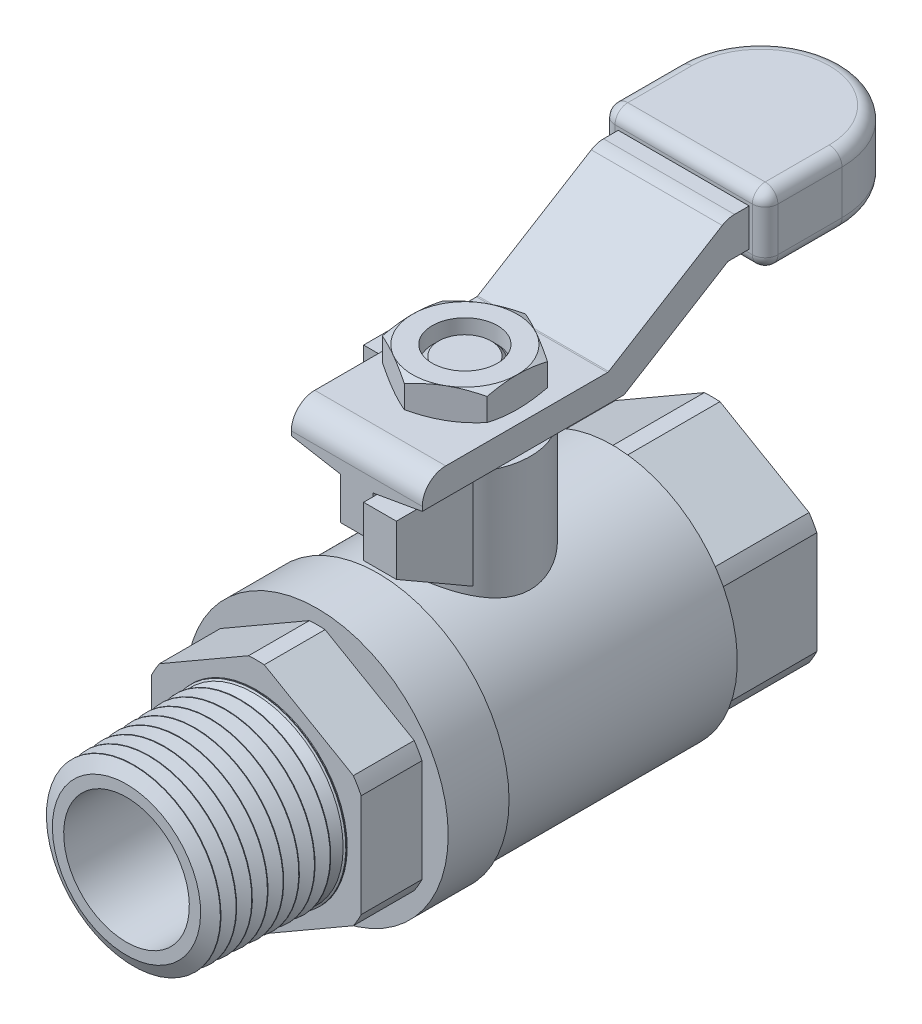
SolidWorks part; units mm, degrees
ref_plane "Front" through (0, 0, 0) normal (0, 0, 1) x (1, 0, 0)
ref_plane "Top" through (0, 0, 0) normal (0, 1, 0) x (1, 0, 0)
ref_plane "Right" through (0, 0, 0) normal (1, 0, 0) x (0, 0, -1)
sketch "Sketch1" plane through (0, -2.9295, 125.5668) normal (1, 0, 0) x (0, 0, -1)
  line L0 (139.5622, 2.9295) -> (139.5622, 11.7701)
  line L1 (139.5622, 11.7701) -> (140.4199, 13.3689) construction
  line L2 (140.4199, 13.3689) -> (141.3756, 11.8268) construction
  line L3 (141.3756, 11.8268) -> (142.2333, 13.4256) construction
  line L4 (142.2333, 13.4256) -> (143.189, 11.8835) construction
  line L5 (141.4083, 11.8877) -> (142.2006, 13.3646)
  line L6 (142.2006, 13.3646) -> (142.2697, 13.3668)
  line L7 (142.2697, 13.3668) -> (143.1526, 11.9422)
  line L8 (143.1526, 11.9422) -> (143.2217, 11.9444)
  line L9 (139.5622, 11.7701) -> (143.189, 11.8835) construction
  line L10 (140.4199, 13.3689) -> (142.2333, 13.4256) construction
  line L11 (139.9911, 12.5695) -> (142.7112, 12.6545) construction
  line L12 (139.5622, 2.9295) -> (125.5668, 2.9295) construction
  line L13 (143.2217, 11.9444) -> (144.014, 13.4213)
  line L14 (139.5949, 11.8311) -> (140.3872, 13.3079)
  line L15 (140.3872, 13.3079) -> (140.4563, 13.3101)
  line L16 (140.4563, 13.3101) -> (141.3392, 11.8856)
  line L17 (141.3392, 11.8856) -> (141.4083, 11.8877)
  line L18 (139.9911, 12.5695) -> (139.5622, 12.5561) construction
  line L19 (139.5622, 12.5561) -> (139.5622, 11.7701) construction
  line L20 (139.9911, -6.7105) -> (139.5622, -6.6971) construction
  line L21 (139.5949, 11.8311) -> (139.5622, 11.7701)
  line L22 (144.014, 13.4213) -> (144.0831, 13.4234)
  line L23 (144.0831, 13.4234) -> (144.966, 11.9989)
  line L24 (144.966, 11.9989) -> (145.0351, 12.0011)
  line L25 (145.0351, 12.0011) -> (145.8274, 13.478)
  line L26 (145.8274, 13.478) -> (145.8965, 13.4801)
  line L27 (145.8965, 13.4801) -> (146.7794, 12.0556)
  line L28 (146.7794, 12.0556) -> (146.8485, 12.0577)
  line L29 (146.8485, 12.0577) -> (147.6408, 13.5346)
  line L30 (147.6408, 13.5346) -> (147.7099, 13.5368)
  line L31 (147.7099, 13.5368) -> (148.5928, 12.1123)
  line L32 (148.5928, 12.1123) -> (148.6619, 12.1144)
  line L33 (148.6619, 12.1144) -> (149.4542, 13.5913)
  line L34 (149.4542, 13.5913) -> (149.5233, 13.5935)
  line L35 (149.5233, 13.5935) -> (150.4062, 12.1689)
  line L36 (150.4062, 12.1689) -> (150.4753, 12.1711)
  line L37 (150.4753, 12.1711) -> (151.2676, 13.648)
  line L38 (151.2676, 13.648) -> (151.3367, 13.6501)
  line L39 (151.3367, 13.6501) -> (152.2196, 12.2256)
  line L40 (152.2196, 12.2256) -> (152.2887, 12.2278)
  line L41 (152.2887, 12.2278) -> (153.081, 13.7046)
  line L42 (153.081, 13.7046) -> (153.1501, 13.7068)
  line L43 (153.1501, 13.7068) -> (154.033, 12.2823)
  line L44 (154.033, 12.2823) -> (154.1021, 12.2844)
  line L45 (154.1021, 12.2844) -> (154.8944, 13.7613)
  line L46 (154.8944, 13.7613) -> (154.9635, 13.7635)
  line L47 (154.9635, 13.7635) -> (155.8464, 12.3389)
  line L48 (155.8464, 12.3389) -> (155.9155, 12.3411)
  line L49 (155.9155, 12.3411) -> (156.7078, 13.818)
  line L50 (156.7078, 13.818) -> (156.7769, 13.8201)
  line L51 (156.7769, 13.8201) -> (157.6598, 12.3956)
  line L52 (157.6598, 12.3956) -> (157.7289, 12.3978)
  line L53 (157.7289, 12.3978) -> (158.5212, 13.8747)
  line L54 (158.5212, 13.8747) -> (158.5903, 13.8768)
  line L55 (158.5903, 13.8768) -> (159.4732, 12.4523)
  line L56 (159.4732, 12.4523) -> (159.5423, 12.4544)
  line L57 (159.5423, 12.4544) -> (160.3346, 13.9313)
  line L58 (160.3346, 13.9313) -> (160.4037, 13.9335)
  line L59 (160.4037, 13.9335) -> (161.2866, 12.509)
  line L60 (161.2866, 12.509) -> (161.3557, 12.5111)
  line L61 (161.3557, 12.5111) -> (162.148, 13.988)
  line L62 (162.148, 13.988) -> (162.2171, 13.9902)
  line L63 (162.2171, 13.9902) -> (163.1, 12.5656)
  line L64 (163.1, 12.5656) -> (163.1691, 12.5678)
  line L65 (163.1691, 12.5678) -> (163.9614, 14.0447)
  line L66 (163.9614, 14.0447) -> (164.0305, 14.0468)
  line L67 (164.0305, 14.0468) -> (164.9134, 12.6223)
  line L68 (164.9134, 12.6223) -> (164.9825, 12.6245)
  line L69 (164.9825, 12.6245) -> (165.7748, 14.1013)
  line L70 (165.7748, 14.1013) -> (165.8439, 14.1035)
  line L71 (165.8439, 14.1035) -> (166.7268, 12.679)
  line L72 (166.7268, 12.679) -> (166.7959, 12.6811)
  line L73 (139.5622, 2.9295) -> (166.7959, 2.9295)
  line L74 (166.7959, 2.9295) -> (166.7959, 12.6811)
  line L75 (140.4217, 13.309) -> (140.4199, 13.3689) construction
  line L76 (142.7112, 12.6545) -> (153.1258, 12.98) construction
  line L77 (153.1258, 12.98) -> (153.1258, 2.9295) construction
  line L78 (153.1258, 12.98) -> (155.0562, 13.0403) construction
  line L79 (155.0562, 13.0403) -> (155.0562, 2.9295) construction
  line L80 (125.5668, 2.9295) -> (85.2062, 2.9295) construction
  line L82 (85.2062, 2.9295) -> (85.2062, 13.0403) construction
  line L84 (153.1258, 12.2539) -> (155.0562, 12.3143) construction
  line L85 (139.5622, 7.3498) -> (125.5668, 7.3498) construction
  line L86 (125.5668, 7.3498) -> (125.5668, 2.9295) construction
  line L87 (155.0562, 13.0403) -> (85.2062, 13.0403) construction
  dimension "D1" = 60
  dimension "E0" = 19.2532
  dimension "Thread Pitch" = 1.8143
  dimension "D4" = 3.58
  dimension "L2 Thread Engagement" = 13.5636
  dimension "l Thread Length" = 15.494
  dimension "Body Length" = 69.85
  dimension "Right Length G" = 29.4894
  dimension "D5" = 54.356
revolve "Revolve1" add sketch "Sketch1" angle 360 about L12
sketch "Sketch6" plane through (0, 0, 0) normal (1, 0, 0) x (0, 0, -1)
  line L0 (29.4894, 0) -> (29.4894, 10.8369)
  line L1 (29.4894, 10.8369) -> (41.2291, 11.2038)
  line L2 (41.2291, 11.2038) -> (41.2291, 0)
  line L3 (41.2291, 0) -> (29.4894, 0)
  line L4 (29.4894, 10.1108) -> (29.4894, 0) construction
  line L5 (13.9954, 0) -> (41.2291, 0) construction
  line L6 (41.2291, 0) -> (41.2291, 9.7516) construction
  line L7 (31.1409, 10.8885) -> (31.2101, 10.8906) construction
revolve "Cut-Revolve3" cut sketch "Sketch6" angle 360 about L3
sketch "Sketch7" plane through (0, 0, 0) normal (1, 0, 0) x (0, 0, -1)
  line L0 (27.559, 9.3244) -> (29.4894, 10.8369)
  line L1 (29.4894, 10.8369) -> (29.4894, 9.3847)
  line L2 (29.4894, 9.3847) -> (27.559, 9.3244)
  line L3 (29.4894, 10.1108) -> (29.4894, 0) construction
  line L4 (14.8203, 10.3784) -> (14.8895, 10.3806) construction
  line L5 (27.559, 9.3244) -> (29.4894, 9.3847) construction
  line L6 (13.9954, 0) -> (27.559, 0) construction
  line L7 (27.559, 0) -> (27.559, 9.3244) construction
  line L8 (13.9954, 0) -> (13.9954, 8.8406) construction
  line L9 (0, 0) -> (13.9954, 0) construction
  line L10 (0, 0) -> (0, 7.493) construction
  line L11 (0, 7.493) -> (12.6478, 7.493) construction
  line L12 (13.9954, 0) -> (13.9954, 8.8406) construction
  line L13 (13.9954, 8.8406) -> (12.6478, 7.493) construction
  dimension "D1" = 45
  dimension "Min ID" = 14.986
revolve "Revolve3" add sketch "Sketch7" angle 360 about L6
pattern_linear "LPattern2" count 2 spacing 54.356 along (0, 0, 1) of bodies 114
sketch "Sketch30" plane through (0, 0, 0) normal (1, 0, 0) x (0, 0, -1)
  line L0 (-40.3606, 0) -> (-40.3606, 10.1108) construction
  line L1 (-40.3606, 7.493) -> (0, 7.493)
  line L2 (-40.3606, 7.493) -> (-40.3606, 0)
  line L3 (-40.3606, 0) -> (0, 0)
  line L4 (0, 7.493) -> (0, 0)
  line L5 (0, 7.493) -> (12.6478, 7.493) construction
  line L6 (13.9954, 0) -> (0, 0) construction
  line L7 (0, 4.4203) -> (0, 0) construction
revolve "Cut-Revolve8" cut sketch "Sketch30" angle 360 about L3
sketch "Sketch29" plane through (0, 0, 0) normal (1, 0, 0) x (0, 0, -1)
  line L0 (0, 0) -> (13.9954, 0) construction
  line L1 (13.9954, 0) -> (13.9954, 8.8406) construction
  line L2 (0, 7.493) -> (12.6478, 7.493) construction
  line L3 (13.9954, 8.8406) -> (12.6478, 7.493) construction
  line L4 (-24.8666, 0) -> (13.9954, 0)
  line L5 (13.9954, 0) -> (13.9954, 8.8406)
  line L6 (-24.8666, 7.493) -> (12.6478, 7.493)
  line L7 (13.9954, 8.8406) -> (12.6478, 7.493)
  line L8 (-24.8666, -10.8369) -> (-24.8666, 10.8369) construction
  line L9 (-24.8666, 0) -> (-24.8666, 7.493)
revolve "Revolve6" add sketch "Sketch29" angle 360 about L4
sketch "Sketch8" plane through (0, 0, 24.8666) normal (0, 0, 1) x (1, 0, 0)
  line L1 (0, 14.4301) -> (-12.4968, 7.215)
  line L2 (-12.4968, 7.215) -> (-12.4968, -7.215)
  line L3 (-12.4968, -7.215) -> (0, -14.4301)
  line L4 (0, -14.4301) -> (12.4968, -7.215)
  line L5 (12.4968, -7.215) -> (12.4968, 7.215)
  line L6 (12.4968, 7.215) -> (0, 14.4301)
  circle A0 centre (0, 0) radius 12.4968 construction
  dimension "Body Hex" = 24.9936
extrude "Extrude1" add sketch "Sketch8" against normal up to surface (54.356 mm away) separate body
sketch "Sketch9" plane through (0, 0, 0) normal (1, 0, 0) x (0, 0, -1)
  line L0 (-17.6095, 7.215) -> (-17.6095, 15.621)
  line L1 (-17.6095, 15.621) -> (-10.3523, 15.621)
  line L2 (-10.3523, 15.621) -> (-10.3523, 15.1811)
  line L3 (-10.3523, 15.1811) -> (-10.0412, 14.87)
  line L4 (-10.0412, 14.87) -> (17.624, 14.87)
  line L5 (17.624, 14.87) -> (17.624, 7.215)
  line L6 (17.624, 7.215) -> (-17.6095, 7.215)
  line L7 (29.4894, 7.215) -> (-24.8666, 7.215) construction
  line L8 (0, 0) -> (0, 7.215) construction
  line L9 (13.9954, 0) -> (13.9954, 8.8406) construction
  line L10 (0, 0) -> (-17.6095, 0) construction
  line L11 (-17.6095, 0) -> (-17.6095, 7.215) construction
  line L12 (-10.0412, 14.87) -> (-10.0412, 14.4301) construction
  line L13 (29.4894, 14.4301) -> (-24.8666, 14.4301) construction
  line L14 (29.4894, 10.1108) -> (29.4894, 14.87) construction
  line L15 (29.4894, 14.87) -> (17.624, 14.87) construction
  line L16 (-24.8666, 14.4301) -> (-24.8666, 15.621) construction
  line L17 (-24.8666, 15.621) -> (-17.6095, 15.621) construction
  dimension "D1" = 3.6286
  dimension "D2" = 31.242
  dimension "D3" = 135
  dimension "D4" = 7.2571
revolve "Revolve4" add sketch "Sketch9" angle 360 about L10
sketch "Sketch10" plane through (0, 0, 0) normal (1, 0, 0) x (0, 0, -1)
  line L0 (0, 7.493) -> (0, 23.8567)
  line L1 (3.8925, 26.4221) -> (3.9179, 26.4221) construction
  line L2 (7.8105, 26.4221) -> (7.8105, 7.493)
  line L3 (7.8105, 7.493) -> (0, 7.493)
  line L4 (0, 0) -> (0, 7.493) construction
  line L5 (-9.0805, 21.1485) -> (-9.0805, 26.6761) construction
  line L6 (-9.0805, 26.6761) -> (10.3505, 26.6761) construction
  line L7 (10.3505, 26.6761) -> (23.5567, 34.7738) construction
  line L8 (-9.0805, 21.1485) -> (-12.8905, 21.1485) construction
  line L9 (-12.8905, 21.1485) -> (-12.8905, 30.4861) construction
  line L10 (-12.8905, 30.4861) -> (9.2754, 30.4861) construction
  line L11 (9.2754, 30.4861) -> (23.5567, 39.243) construction
  line L12 (23.5567, 39.243) -> (23.5567, 34.7738) construction
  line L13 (17.624, 14.87) -> (-10.0412, 14.87) construction
  line L14 (23.5567, 41.148) -> (23.5567, 32.8688) construction
  line L15 (23.5567, 32.8688) -> (44.9834, 32.8688) construction
  line L16 (44.9834, 32.8688) -> (44.9834, 41.148) construction
  line L17 (44.9834, 41.148) -> (23.5567, 41.148) construction
  line L18 (-1.8075, 30.4861) -> (-1.8075, 26.6761) construction
  line L19 (16.416, 34.8645) -> (18.4076, 31.6165) construction
  line L20 (-7.8105, 26.4221) -> (-7.8105, 7.493) construction
  line L21 (0, 7.493) -> (12.6478, 7.493) construction
  line L22 (23.5567, 32.8688) -> (23.5567, 14.87) construction
  line L23 (29.4894, 14.87) -> (17.624, 14.87) construction
  line L24 (-10.3523, 15.621) -> (-10.3523, 21.1485) construction
  line L25 (-10.3523, 21.1485) -> (-12.8905, 21.1485) construction
  line L26 (3.8925, 26.4221) -> (3.8925, 32.8688)
  line L27 (3.8925, 32.8688) -> (0, 32.8688)
  line L28 (3.8925, 26.4221) -> (3.8925, 23.8821)
  line L29 (3.8925, 23.8821) -> (0, 23.8821)
  line L30 (0, 23.8567) -> (3.9179, 23.8567)
  line L31 (3.9179, 23.8567) -> (3.9179, 26.4221)
  line L32 (3.9179, 26.4221) -> (7.8105, 26.4221)
  line L33 (0, 23.8567) -> (0, 23.8821) construction
  line L34 (0, 23.8821) -> (0, 32.8688)
  line L35 (-3.8925, 26.4221) -> (-3.8925, 32.8688) construction
  line L36 (3.9179, 23.8567) -> (3.9179, 14.87) construction
  line L37 (3.9179, 14.87) -> (23.5567, 14.87) construction
  point P26 (23.5567, 37.0084)
  dimension "Handle Height" = 41.148
  dimension "Handle Length" = 44.9834
  dimension "D3" = 15.621
  dimension "D5" = 17.9988
  dimension "D6" = 3.81
  dimension "D7" = 1.27
  dimension "D8" = 0.254
  dimension "D9" = 2.54
  dimension "D11" = 0.0254
  dimension "D12" = 0.0254
  dimension "D13" = 8.9867
  dimension "D14" = 2.54
  dimension "D2" = 1.905
revolve "Revolve5" add sketch "Sketch10" angle 360 about L4
chamfer "Chamfer1" distance 0.762 angle 45 1 edges at (0, 32.8688, -3.8925)
sketch "Sketch20" plane through (0, 0, 0) normal (1, 0, 0) x (0, 0, -1)
  line L0 (3.8925, 32.8688) -> (-3.8926, 32.8688) construction
  line L1 (-3.8926, 32.8688) -> (-3.8925, 32.075) construction
  line L2 (-3.8925, 32.075) -> (3.8925, 32.8688) construction
  line L3 (3.8925, 32.8688) -> (3.9026, 32.7701) construction
  line L4 (3.9026, 32.7701) -> (3.9731, 32.0791)
  line L5 (3.9731, 32.0791) -> (3.5205, 32.2823)
  line L6 (3.5205, 32.2823) -> (3.5004, 32.4797)
  line L7 (3.5004, 32.4797) -> (3.9026, 32.7701)
  line L8 (3.5104, 32.381) -> (3.9378, 32.4246) construction
  line L9 (3.8925, 32.8688) -> (3.8926, 32.42) construction
  line L10 (3.8926, 32.42) -> (-3.8925, 31.6262) construction
  line L11 (-3.8925, 31.6262) -> (-3.8925, 32.075) construction
  line L12 (-0.0862, 32.8688) -> (0.0862, 31.1774) construction
  line L13 (-3.8925, 26.4221) -> (-3.8925, 32.8688) construction
  line L14 (3.8925, 26.4221) -> (3.8925, 32.8688) construction
  line L15 (3.8925, 32.8688) -> (0, 32.8688) construction
  point P13 (0, 32.0231)
  dimension "D2" = 0.1984
  dimension "D3" = 0.7937
  dimension "D4" = 60
  dimension "D5" = 0.7937
revolve "Cut-Revolve6" cut sketch "Sketch20" angle 360 about L12
pattern_linear "LPattern1" count 2 spacing 0.7937 along (0, 1, 0) count 11 spacing 0.7937 along (0, -1, 0) of "Cut-Revolve6"
sketch "Sketch26" plane through (0, 23.8567, 0) normal (0, 1, 0) x (-1, 0, 0)
  circle A1 centre (0, 0) radius 3.9179
  circle A2 centre (0, 0) radius 3.9179
  dimension "D1" = 0
extrude "Extrude8" add sketch "Sketch26" along normal blind 0.127
sketch "Sketch16" plane through (0, 0, 0) normal (1, 0, 0) x (0, 0, -1)
  line L0 (-24.8666, 7.215) -> (-24.8666, 14.4301) construction
  line L1 (29.4894, 14.4301) -> (17.624, 14.4301)
  line L2 (29.4894, 14.4301) -> (29.4894, 13.9221)
  line L3 (29.4894, 13.9221) -> (17.624, 13.9221)
  line L4 (17.624, 14.4301) -> (17.624, 13.9221)
  line L5 (-24.8666, 14.4301) -> (-17.6095, 14.4301)
  line L6 (-24.8666, 14.4301) -> (-24.8666, 13.9221)
  line L7 (-24.8666, 13.9221) -> (-17.6095, 13.9221)
  line L8 (-17.6095, 14.4301) -> (-17.6095, 13.9221)
  line L9 (29.4894, 14.4301) -> (29.4894, 7.215) construction
  line L10 (17.624, -14.87) -> (17.624, 14.87) construction
  line L11 (-17.6095, 15.621) -> (-17.6095, -15.621) construction
  line L12 (-17.6095, 14.4301) -> (-24.8666, 14.4301) construction
  line L13 (0, 0) -> (-24.8666, 0) construction
  line L14 (-24.8666, 0) -> (-24.8666, 13.9221) construction
  dimension "D1" = 0.508
revolve "Cut-Revolve5" cut sketch "Sketch16" angle 360 about L13
combine bodies "Combine1" operation type subtract main body 126 bodies to subtract 151
combine bodies "Combine2" operation type add bodies to combine 150 123
sketch "Sketch11" plane through (0, 0, 0) normal (1, 0, 0) x (0, 0, -1)
  line L1 (9.2754, 30.4861) -> (23.5567, 39.243) construction
  line L2 (10.3505, 26.6761) -> (23.5567, 34.7738) construction
  line L3 (-9.0805, 26.6761) -> (10.3505, 26.6761) construction
  line L4 (-9.0805, 21.1485) -> (-9.0805, 26.6761) construction
  line L5 (-12.8905, 30.4861) -> (9.2754, 30.4861) construction
  line L6 (-12.8905, 21.1485) -> (-12.8905, 30.4861) construction
  line L7 (43.0784, 34.7738) -> (43.0784, 39.243)
  line L8 (9.2754, 30.4861) -> (23.5567, 39.243)
  line L9 (10.3505, 26.6761) -> (23.5567, 34.7738)
  line L10 (-9.0805, 26.6761) -> (10.3505, 26.6761)
  line L11 (-9.0805, 21.1485) -> (-9.0805, 26.6761)
  line L12 (-12.8905, 30.4861) -> (9.2754, 30.4861)
  line L13 (-12.8905, 21.1485) -> (-12.8905, 30.4861)
  line L14 (-9.0805, 21.1485) -> (-12.8905, 21.1485) construction
  line L15 (-9.0805, 21.1485) -> (-12.8905, 21.1485)
  line L16 (23.5567, 39.243) -> (43.0784, 39.243)
  line L17 (23.5567, 34.7738) -> (43.0784, 34.7738)
  line L18 (44.9834, 32.8688) -> (44.9834, 41.148) construction
  dimension "D1" = 1.905
extrude "Extrude2" add sketch "Sketch11" along normal mid plane 15.621 separate body
sketch "Sketch21" plane through (0, 30.4861, 0) normal (0, 1, 0) x (-1, 0, 0)
  circle A0 centre (0, 0) radius 3.918
extrude "Cut-Extrude1" cut sketch "Sketch21" against normal through all
fillet "Fillet1" radius 0.254 3 edges at (0, 34.7738, -23.5567) (0, 30.4861, -9.2754) (0, 26.6761, 9.0805)
fillet "Fillet2" radius 2.794 3 edges at (0, 30.4861, 12.8905) (0, 39.243, -23.5567) (0, 26.6761, -10.3505)
fillet "Fillet3" radius 7.8105 2 edges at (-7.8105, 37.0084, -43.0784) (7.8105, 37.0084, -43.0784)
sketch "Sketch12" plane through (0, 39.243, 0) normal (0, 1, 0) x (-1, 0, 0)
  line L0 (9.7155, -26.0967) -> (-9.7155, -26.0967)
  line L1 (-9.7155, -26.0967) -> (-9.7155, -35.2679)
  line L2 (9.7155, -35.2679) -> (9.7155, -26.0967)
  line L3 (-7.8105, -35.2679) -> (-7.8105, -24.3451) construction
  line L4 (0, -44.9834) -> (0, -23.5567) construction
  arc A0 (-9.7155, -35.2679) -> (9.7155, -35.2679) centre (0, -35.2679) ccw
  arc A1 (-7.8105, -35.2679) -> (0, -43.0784) centre (0, -35.2679) ccw construction
  dimension "D1" = 1.905
  dimension "D2" = 2.54
extrude "Extrude3" add sketch "Sketch12" along normal blind 1.905 separate body
sketch "Sketch13" plane through (0, 34.7738, 0) normal (0, -1, 0) x (1, 0, 0)
  line L3 (9.7155, -26.0967) -> (-9.7155, -26.0967)
  line L4 (9.7155, -35.2679) -> (9.7155, -26.0967)
  line L5 (-9.7155, -26.0967) -> (-9.7155, -35.2679)
  line L6 (9.7155, -26.0967) -> (-9.7155, -26.0967)
  line L7 (9.7155, -35.2679) -> (9.7155, -26.0967)
  line L8 (-9.7155, -26.0967) -> (-9.7155, -35.2679)
  arc A1 (-9.7155, -35.2679) -> (9.7155, -35.2679) centre (0, -35.2679) ccw
  arc A2 (-9.7155, -35.2679) -> (9.7155, -35.2679) centre (0, -35.2679) ccw
  dimension "D1" = 0
extrude "Extrude4" add sketch "Sketch13" along normal blind 1.905 separate body
sketch "Sketch14" plane through (0, 39.243, 0) normal (0, -1, 0) x (1, 0, 0)
  line L0 (-7.8105, -35.2679) -> (-7.8105, -24.3451) construction
  line L1 (7.8105, -35.2679) -> (7.8105, -24.3451) construction
  line L2 (-7.8105, -35.2679) -> (-7.8105, -26.0967)
  line L3 (9.7155, -26.0967) -> (-9.7155, -26.0967)
  line L4 (9.7155, -35.2679) -> (9.7155, -26.0967)
  line L5 (-9.7155, -26.0967) -> (-9.7155, -35.2679)
  line L6 (9.7155, -26.0967) -> (7.8105, -26.0967)
  line L7 (9.7155, -35.2679) -> (9.7155, -26.0967)
  line L8 (-9.7155, -26.0967) -> (-9.7155, -35.2679)
  line L9 (7.8105, -35.2679) -> (7.8105, -26.0967)
  line L10 (-7.8105, -26.0967) -> (-9.7155, -26.0967)
  arc A0 (-7.8105, -35.2679) -> (0, -43.0784) centre (0, -35.2679) ccw construction
  arc A1 (-9.7155, -35.2679) -> (9.7155, -35.2679) centre (0, -35.2679) ccw
  arc A2 (-9.7155, -35.2679) -> (9.7155, -35.2679) centre (0, -35.2679) ccw
  arc A3 (0, -43.0784) -> (7.8105, -35.2679) centre (0, -35.2679) ccw construction
  arc A4 (-7.8105, -35.2679) -> (0, -43.0784) centre (0, -35.2679) ccw
  arc A5 (0, -43.0784) -> (7.8105, -35.2679) centre (0, -35.2679) ccw
  dimension "D1" = 0
extrude "Extrude5" add sketch "Sketch14" along normal up to surface (4.4692 mm away) up to face at (0, 34.7738, -33.1112)
fillet "Fillet4" radius 1.524 10 edges at (-9.7155, 41.148, -30.6823) (0, 41.148, -44.9834) (-9.7155, 32.8688, -30.6823) (0, 32.8688, -44.9834) (9.7155, 41.148, -30.6823) (9.7155, 32.8688, -30.6823) (9.7155, 37.0084, -26.0967) (-9.7155, 37.0084, -26.0967) (0, 41.148, -26.0967) (0, 32.8688, -26.0967)
sketch "Sketch15" plane through (0, 30.4861, 0) normal (0, 1, 0) x (-1, 0, 0)
  line L1 (0, 7.215) -> (-6.2484, 3.6075)
  line L2 (-6.2484, 3.6075) -> (-6.2484, -3.6075)
  line L3 (-6.2484, -3.6075) -> (0, -7.215)
  line L4 (0, -7.215) -> (6.2484, -3.6075)
  line L5 (6.2484, -3.6075) -> (6.2484, 3.6075)
  line L6 (6.2484, 3.6075) -> (0, 7.215)
  circle A0 centre (0, 0) radius 6.2484 construction
  dimension "D1" = 12.4968
extrude "Extrude6" add sketch "Sketch15" along normal blind 3.5947 separate body
sketch "Sketch22" plane through (0, 0, 0) normal (1, 0, 0) x (0, 0, -1)
  line L0 (6.2484, 34.0808) -> (7.215, 34.0808)
  line L1 (0, 34.0808) -> (3.8925, 34.0808)
  line L2 (0, 34.0808) -> (0, 30.4861)
  line L3 (0, 30.4861) -> (3.8925, 30.4861)
  line L4 (3.8925, 34.0808) -> (3.8925, 30.4861)
  line L5 (7.215, 34.0808) -> (7.215, 33.63)
  line L6 (7.215, 33.63) -> (6.2484, 34.0808)
  line L7 (6.2484, 30.4861) -> (7.215, 30.4861)
  line L8 (7.215, 30.4861) -> (7.215, 30.9368)
  line L9 (7.215, 30.9368) -> (6.2484, 30.4861)
  line L10 (7.215, 34.0808) -> (7.215, 30.4861) construction
  line L11 (3.6075, 34.0808) -> (7.215, 34.0808) construction
  line L12 (-12.8905, 30.4861) -> (9.2754, 30.4861) construction
  line L13 (0, 23.8821) -> (0, 32.8688) construction
  line L14 (3.8925, 26.4221) -> (3.8925, 32.8688) construction
  line L15 (0, 0) -> (0, 30.4861) construction
  line L16 (6.2484, 30.4861) -> (6.2484, 34.0808) construction
  dimension "D1" = 25
  dimension "D2" = 12.4968
revolve "Cut-Revolve7" cut sketch "Sketch22" angle 360 about L15
sketch "Sketch23" plane through (0, 0, 12.8905) normal (0, 0, 1) x (1, 0, 0)
  line L0 (-7.8105, 27.1841) -> (-1.9526, 26.1512)
  line L1 (-1.9526, 26.1512) -> (-1.9526, 21.1485)
  line L2 (-1.9526, 21.1485) -> (1.9526, 21.1485)
  line L3 (1.9526, 21.1485) -> (1.9526, 26.1512)
  line L4 (1.9526, 26.1512) -> (7.8105, 27.1841)
  line L5 (7.8105, 27.1841) -> (7.8105, 19.8785)
  line L6 (7.8105, 19.8785) -> (-7.8105, 19.8785)
  line L7 (-7.8105, 19.8785) -> (-7.8105, 27.1841)
  line L8 (-1.9526, 21.1485) -> (-7.8105, 21.1485) construction
  line L9 (1.9526, 21.1485) -> (7.8105, 21.1485) construction
  line L10 (0, 21.1485) -> (0, 19.8785) construction
  line L11 (-7.8105, 27.1841) -> (7.8105, 27.1841) construction
  line L12 (-1.9526, 26.1512) -> (1.9526, 26.1512) construction
  line L13 (-7.8105, 27.6921) -> (-7.8105, 21.1485) construction
  line L14 (7.8105, 27.6921) -> (7.8105, 21.1485) construction
  line L15 (7.8105, 21.1485) -> (-7.8105, 21.1485) construction
  line L16 (7.8105, 27.6921) -> (-7.8105, 27.6921) construction
  dimension "D1" = 3.9052
  dimension "D2" = 10
  dimension "D3" = 0.508
  dimension "D4" = 1.27
  dimension "D5" = 15.621
extrude "Cut-Extrude2" cut sketch "Sketch23" against normal through all
sketch "Sketch24" plane through (0, 0, 12.8905) normal (0, 0, 1) x (1, 0, 0)
  line L0 (-1.9526, 26.1512) -> (1.9526, 26.1512) construction
  line L1 (2.0796, 25.8972) -> (5.9849, 25.8972)
  line L2 (2.0796, 25.8972) -> (2.0796, 19.8785)
  line L3 (2.0796, 19.8785) -> (5.9849, 19.8785)
  line L4 (5.9849, 25.8972) -> (5.9849, 19.8785)
  line L6 (-1.9526, 21.1485) -> (1.9526, 21.1485) construction
  line L8 (1.9526, 21.1485) -> (1.9526, 26.1512) construction
  dimension "D1" = 0.254
  dimension "D3" = 1.27
  dimension "D2" = 0.127
  dimension "D4" = 3.9052
extrude "Extrude7" add sketch "Sketch24" along normal blind 1.27 and the other way up to surface other way up to face at (0.692, 14.8539, 7.7798)
ref_axis "Axis1" through (0, -15.2056, 0) along (0, 1, 0)
ref_plane "Plane1" through (0, 0, 0) normal (-0.7071, 0, -0.7071) x (-0.7071, 0, 0.7071)
mirror "Mirror3" about plane through (0, 0, 0) normal (-0.7071, 0, -0.7071) of "Extrude7"
draft "Draft1" type of draft neutral plane draft angle 30 faces to draft 1 face at (4.0799, 19.8785, 10.2912) neutral plane through (2.0796, 19.8785, 14.1605) neutral plane normal (0, 0, 1) parameters "D1"=30
draft "Draft2" type of draft neutral plane draft angle 30 faces to draft 1 face at (-10.2912, 19.8785, -4.0799) neutral plane through (-14.1605, 19.8785, -2.0796) neutral plane normal (-1, 0, 0) parameters "D1"=30
equation "\"D2@Sketch1\"=\"Thread Pitch@Sketch1\"*.033"
equation "\"D2@Sketch9\"=\"Body Hex@Sketch8\"*1.25"
equation "\"D1@Sketch9\" = \"Thread Pitch@Sketch1\"*2"
equation "\"D4@Sketch9\"=\"D1@Sketch9\"*2"
equation "\"D3@Sketch10\"=\"Body Hex@Sketch8\"*.625"
equation "\"D1@Extrude2\"=\"D3@Sketch10\""
equation "\"D1@Fillet3\"=\"D1@Extrude2\"/2"
equation "\"D1@Sketch15\"=\"D1@Extrude2\"*.8"
equation "\"D2@LPattern1\"=\"D13@Sketch10\"/\"D3@Sketch20\""
equation "\"D2@Sketch22\"=\"D1@Sketch15\""
equation "\"D1@Extrude6\"=\"D13@Sketch10\"/2.5"
equation "\"D1@Sketch23\"=\"D5@Sketch23\"/4"
equation "\"D4@Sketch24\"=\"D1@Sketch23\""
equation "\"D3@LPattern2\"=\"D5@Sketch1\""
